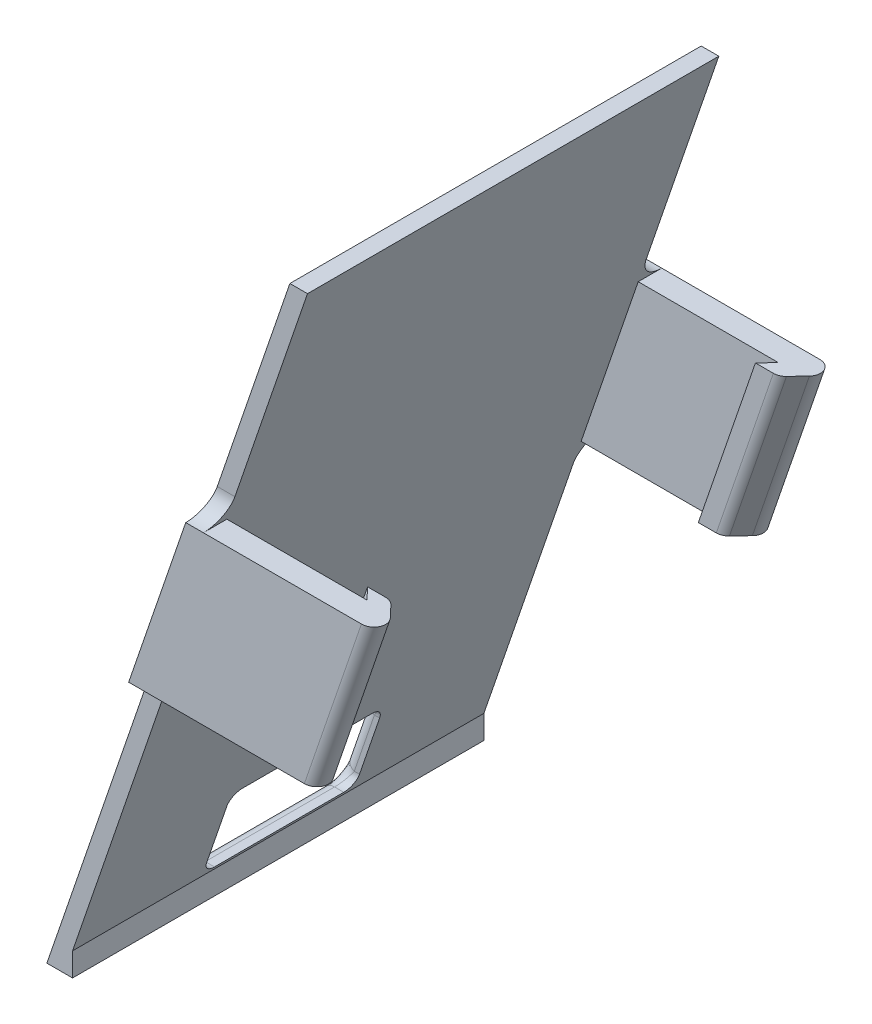
SolidWorks part; units mm, degrees
ref_plane "前视基准面" through (0, 0, 0) normal (0, 0, 1) x (1, 0, 0)
ref_plane "上视基准面" through (0, 0, 0) normal (0, 1, 0) x (1, 0, 0)
ref_plane "右视基准面" through (0, 0, 0) normal (1, 0, 0) x (0, 0, -1)
sketch "草图1" plane through (0, 0, 0) normal (0, 0, 1) x (1, 0, 0)
  line L0 (0, 0) -> (0, 2)
  line L1 (0, 2) -> (19.9917, 60.4243)
  line L2 (19.9917, 60.4243) -> (18.4917, 60.4243)
  line L3 (18.4917, 60.4243) -> (-2.1844, 0)
  line L4 (-2.1844, 0) -> (0, 0)
  dimension "D2" = 2
  dimension "D3" = 61.75
  dimension "D4" = 1.5
  dimension "D5" = 71.11
extrude "凸台-拉伸1" add sketch "草图1" along normal blind 35
sketch3d "3D草图1"
  line L0 (-2.1844, 0, 35) -> (-2.1844, 0, 0) construction
  line L1 (-2.1844, 0, 0) -> (-2.1844, 0, 35)
  line L3 (-2.1844, 9.224, 12) -> (-2.1844, 9.224, 23)
  line L4 (-2.1844, 8.224, 11) -> (-2.1844, 3.224, 11)
  line L5 (-2.1844, 2.224, 12) -> (-2.1844, 2.224, 23)
  line L6 (-2.1844, 8.224, 24) -> (-2.1844, 3.224, 24)
  arc A0 (-2.1844, 8.224, 24) -> (-2.1844, 9.224, 23) centre (-2.1844, 8.224, 23) ccw
  arc A1 (-2.1844, 2.224, 23) -> (-2.1844, 3.224, 24) centre (-2.1844, 3.224, 23) ccw
  arc A2 (-2.1844, 3.224, 11) -> (-2.1844, 2.224, 12) centre (-2.1844, 3.224, 12) ccw
  arc A3 (-2.1844, 8.224, 11) -> (-2.1844, 9.224, 12) centre (-2.1844, 8.224, 12) ccw
  point P10 (-2.1844, 2.224, 17.5)
  point P11 (-2.1844, 0, 17.5)
  point P14 (-2.1844, 9.224, 24)
  point P15 (-3.1844, 8.224, 23)
  point P18 (-2.1844, 2.224, 24)
  point P19 (-3.1844, 3.224, 23)
  point P22 (-2.1844, 2.224, 11)
  point P23 (-3.1844, 3.224, 12)
  point P26 (-2.1844, 9.224, 11)
  point P27 (-1.1844, 8.224, 12)
  dimension "D3" = 1
  dimension "D1" = 13
  dimension "D2" = 7
extrude "切除-拉伸1" cut sketch "3D草图1" along direction (1, 0, 0) on the side against the normal blind 17 contours L4 A2 L5 A1 L6 A0 L3 A3
sketch "草图2" plane through (0, 0, 35) normal (0, 0, 1) x (1, 0, 0)
  line L2 (0, 2) -> (19.9917, 60.4243) construction
  point P2 (13.1316, 40.3761)
sketch3d "3D草图2"
  line L0 (11.6316, 40.3761, 35) -> (13.1316, 40.3761, 35)
  line L1 (13.1316, 40.3761, 35) -> (25.0533, 40.3761, 35)
  line L2 (18.4917, 60.4243, 35) -> (-2.1844, 0, 35) construction
  line L3 (25.0533, 40.3761, 35) -> (24.1047, 40.3761, 34)
  line L4 (24.1047, 40.3761, 34) -> (26.1047, 40.3761, 34)
  line L5 (26.1047, 40.3761, 34) -> (28.9505, 40.3761, 37)
  line L6 (28.9505, 40.3761, 37) -> (11.6316, 40.3761, 37)
  line L7 (11.6316, 40.3761, 37) -> (11.6316, 40.3761, 35)
  line L8 (13.1316, 40.3761, 35) -> (13.1316, 40.3761, 0) construction
  line L9 (0, 2, 0) -> (19.9917, 60.4243, 0) construction
  line L10 (11.6316, 40.3761, -2) -> (11.6316, 40.3761, 0)
  line L11 (28.9505, 40.3761, -2) -> (11.6316, 40.3761, -2)
  line L12 (26.1047, 40.3761, 1) -> (28.9505, 40.3761, -2)
  line L13 (24.1047, 40.3761, 1) -> (26.1047, 40.3761, 1)
  line L14 (25.0533, 40.3761, 0) -> (24.1047, 40.3761, 1)
  line L15 (13.1316, 40.3761, 0) -> (25.0533, 40.3761, 0)
  line L16 (11.6316, 40.3761, 0) -> (13.1316, 40.3761, 0)
  point P1 (11.6316, 40.3761, 35)
  point P14 (13.1316, 40.3761, 17.5)
  dimension "D1" = 2
  dimension "D2" = 2
  dimension "D3" = 1
extrude "凸台-拉伸7" add sketch "3D草图2" along direction (0.3238, 0.9461, 0) on the side of the normal blind 15
fillet "圆角13" radius 2 4 edges
fillet "圆角15" radius 1 4 edges
fillet "圆角16" radius 1 8 edges at (0.8717, 8.9311, 11.2929) (0.9719, 9.224, 17.5) (0.8717, 8.9311, 23.7071) (-0.2257, 5.724, 24) (-1.3231, 2.5169, 23.7071) (-1.4233, 2.224, 17.5) (-1.3231, 2.5169, 11.2929) (-0.2257, 5.724, 11)
